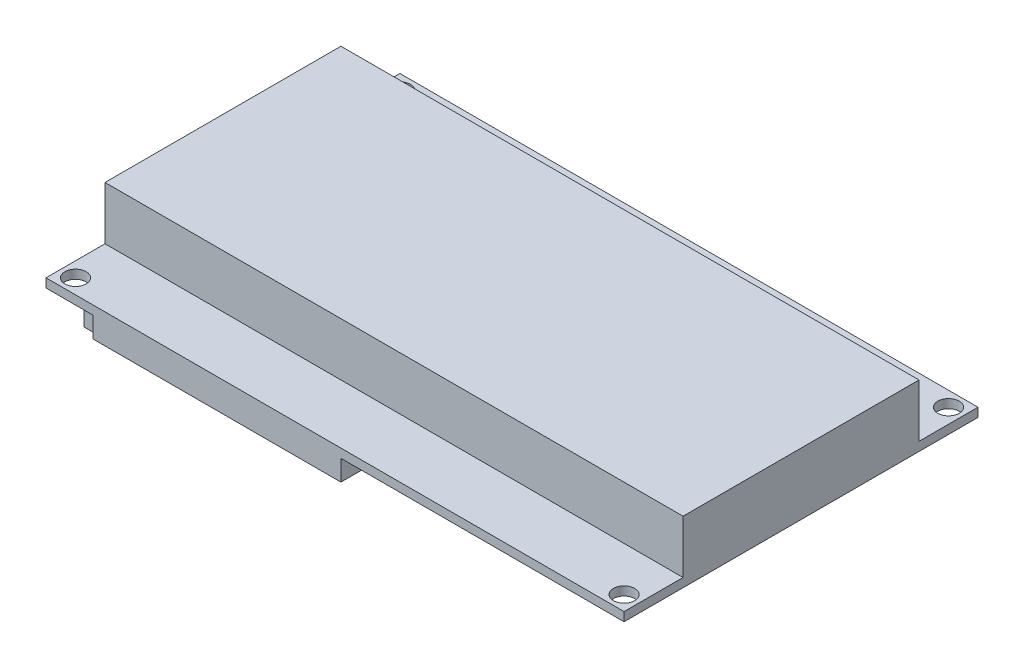
SolidWorks part; units mm, degrees
ref_plane "Ebene vorne" through (0, 0, 0) normal (0, 0, 1) x (1, 0, 0)
ref_plane "Ebene oben" through (0, 0, 0) normal (0, 1, 0) x (1, 0, 0)
ref_plane "Ebene rechts" through (0, 0, 0) normal (1, 0, 0) x (0, 0, -1)
sketch "Skizze1" plane through (0, 0, 0) normal (0, 1, 0) x (1, 0, 0)
  line L1 (0, 0) -> (-49, 0)
  line L2 (0, 0) -> (0, -30)
  line L3 (0, -30) -> (-49, -30)
  line L4 (-49, 0) -> (-49, -30)
  dimension "D1" = 30
  dimension "D2" = 49
extrude "Aufsatz-Linear austragen1" add sketch "Skizze1" along normal blind 1.5
sketch "Skizze2" plane through (0, 1.5, 0) normal (0, 1, 0) x (1, 0, 0)
  line L0 (-49, 0) -> (-49, -30) construction
  line L1 (0, 0) -> (-49, 0)
  line L2 (0, 0) -> (0, -20)
  line L3 (0, -20) -> (-49, -20)
  line L4 (-49, 0) -> (-49, -20)
  dimension "D1" = 20
extrude "Aufsatz-Linear austragen2" add sketch "Skizze2" along normal blind 9
sketch "Skizze3" plane through (0, 1.5, 0) normal (0, 1, 0) x (1, 0, 0)
  line L0 (0, -30) -> (0, -20) construction
  line L1 (0, 0) -> (-49, 0) construction
  circle A0 centre (-46.5, -27.5) radius 1.8
  dimension "D1" = 46.5
  dimension "D3" = 3.6
  dimension "D2" = 27.5
extrude "Schnitt-Linear austragen1" cut sketch "Skizze3" against normal through all and the other way through all
mirror "Spiegeln1" about plane through (0, 1.5, 0) normal (-1, 0, 0) of bodies 114
mirror "Spiegeln2" about plane through (0, 1.5, 0) normal (0, 0, 1) of bodies 115
sketch "Skizze4" plane through (0, 0, 0) normal (0, -1, 0) x (1, 0, 0)
  line L0 (-49, 30) -> (49, 30) construction
  line L1 (-41, 30) -> (1, 30)
  line L2 (-41, 30) -> (-41, 9.6)
  line L3 (-41, 9.6) -> (1, 9.6)
  line L4 (1, 30) -> (1, 9.6)
  line L5 (-49, -30) -> (-49, 30) construction
  dimension "D1" = 50
  dimension "D2" = 20.4
  dimension "D3" = 42
extrude "Aufsatz-Linear austragen3" add sketch "Skizze4" along normal blind 3.5
sketch "Skizze5" plane through (0, -3.5, 0) normal (0, -1, 0) x (1, 0, 0)
  line L0 (-14.9201, 19.8) -> (1, 19.8) construction
  line L1 (-38.5, 24.8) -> (-47.8, 24.8)
  line L2 (-38.5, 24.8) -> (-38.5, 14.8)
  line L3 (-38.5, 14.8) -> (-47.8, 14.8)
  line L4 (-47.8, 24.8) -> (-47.8, 14.8)
  line L5 (-31.1623, 17.7206) -> (-25.9602, 17.7206)
  line L6 (-31.1623, 17.7206) -> (-31.1623, 12.3797)
  line L7 (-31.1623, 12.3797) -> (-25.9602, 12.3797)
  line L8 (-25.9602, 17.7206) -> (-25.9602, 12.3797)
  line L9 (-14.9201, 14.8486) -> (-20.8124, 14.8486)
  line L10 (-14.9201, 14.8486) -> (-14.9201, 24.7514)
  line L11 (-14.9201, 24.7514) -> (-20.8124, 24.7514)
  line L12 (-20.8124, 14.8486) -> (-20.8124, 24.7514)
  line L13 (-1.5, 19.8) -> (7.8, 19.8)
  line L14 (-1.5, 19.8) -> (-1.5, 15)
  line L15 (-1.5, 15) -> (7.8, 15)
  line L16 (7.8, 19.8) -> (7.8, 15)
  line L17 (1, 9.6) -> (1, 30) construction
  line L18 (-41, 19.8) -> (-47.8, 19.8) construction
  line L19 (-41, 30) -> (-41, 9.6) construction
  dimension "D1" = 10
  dimension "D2" = 9.3
  dimension "D3" = 2.5
  dimension "D4" = 9.3
  dimension "D5" = 2.5
  dimension "D6" = 4.8
extrude "Aufsatz-Linear austragen4" add sketch "Skizze5" along normal blind 4.2
